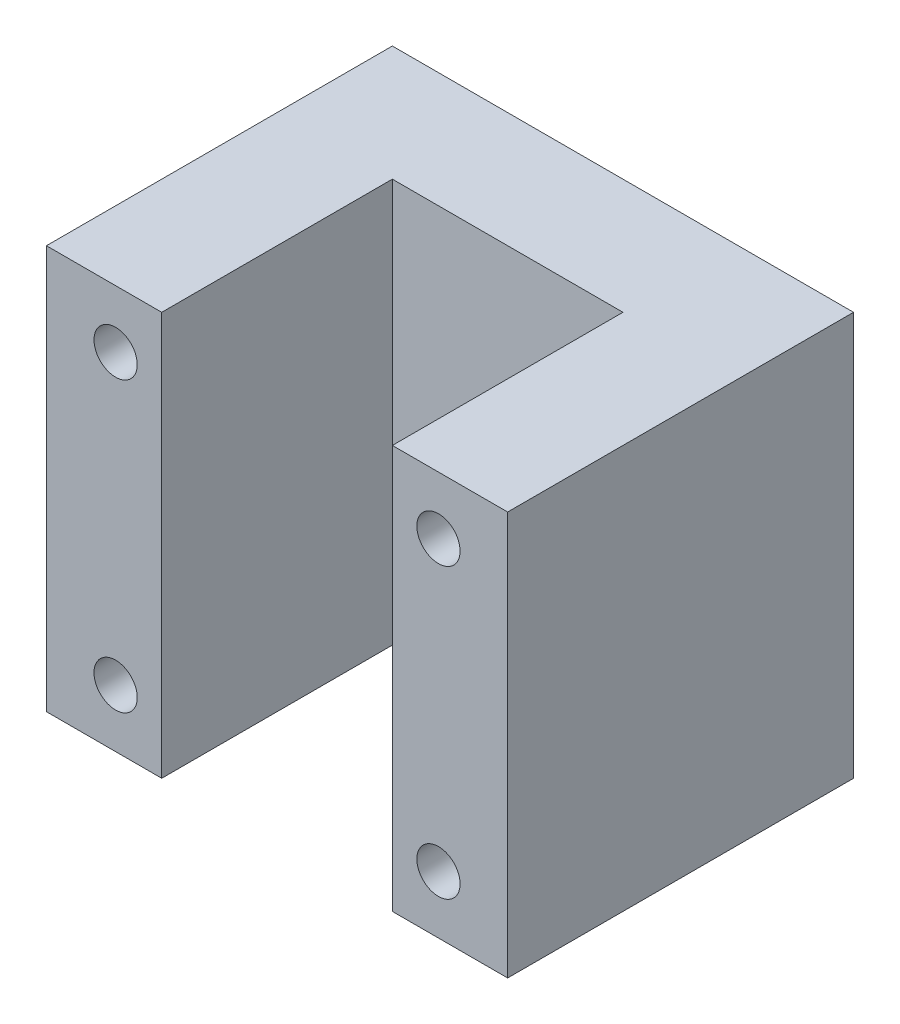
SolidWorks part; units mm, degrees
ref_plane "Front Plane" through (0, 0, 0) normal (0, 0, 1) x (1, 0, 0)
ref_plane "Top Plane" through (0, 0, 0) normal (0, 1, 0) x (1, 0, 0)
ref_plane "Right Plane" through (0, 0, 0) normal (1, 0, 0) x (0, 0, -1)
sketch "Sketch1" plane through (0, 0, 0) normal (0, 1, 0) x (1, 0, 0)
  line L0 (-20, 20) -> (20, 20)
  line L2 (-10, -10) -> (-10, 10)
  line L3 (-10, 10) -> (10, 10)
  line L4 (10, -10) -> (10, 10)
  line L5 (-10, -10) -> (10, 10) construction
  line L6 (-10, 10) -> (10, -10) construction
  line L7 (20, -10) -> (20, 20)
  line L9 (-20, -10) -> (-20, 20)
  line L13 (-20, -20) -> (20, -20) construction
  line L14 (-10, -10) -> (10, -10) construction
  line L15 (-10, -10) -> (-20, -10)
  line L16 (10, -10) -> (20, -10)
  line L17 (-20, -20) -> (-20, 20) construction
  line L18 (20, -20) -> (20, 20) construction
  point P0 (0, 0)
  point P10 (-20.5484, -12.6471)
  dimension "D1" = 20
  dimension "D2" = 20
  dimension "D3" = 10
extrude "Boss-Extrude1" add sketch "Sketch1" along normal mid plane 35
sketch "Sketch3" plane through (0, 0, 0) normal (0, 0, 1) x (1, 0, 0)
  circle A0 centre (-14, -12.5) radius 2.125 construction
  circle A1 centre (14, -12.5) radius 2.125 construction
  circle A2 centre (14, 12.5) radius 2.125 construction
  circle A3 centre (-14, 12.5) radius 2.125 construction
  circle A4 centre (-14, -12.5) radius 2.125
  circle A5 centre (14, -12.5) radius 2.125
  circle A6 centre (14, 12.5) radius 2.125
  circle A7 centre (-14, 12.5) radius 2.125
  circle A8 centre (-14, 12.5) radius 3.375
  circle A9 centre (14, 12.5) radius 3.375
  circle A10 centre (14, -12.5) radius 3.375
  circle A11 centre (-14, -12.5) radius 3.375
  circle A12 centre (0, 0) radius 3
  circle A13 centre (-14, 12.5) radius 1.875
  circle A14 centre (14, 12.5) radius 1.875
  circle A15 centre (-14, -12.5) radius 1.875
  circle A16 centre (14, -12.5) radius 1.875
  dimension "D2" = 6
  dimension "D1" = 1.25
  dimension "D3" = 1.5
extrude "Cut-Extrude1" cut sketch "Sketch3" along normal blind 10 and the other way through all from surface contours A8 A7 | A11 A4 | A10 A5 | A9 A6 | A6 | A5 | A4 | A7 region at (-16.0649, -12.5, 0) region at (11.9351, -12.5, 0) region at (11.9351, 12.5, 0) region at (-16.0649, 12.5, 0) region at (-17.2795, 12.5, 0) region at (10.7205, 12.5, 0) region at (10.7205, -12.5, 0) region at (-17.2795, -12.5, 0) starting at face at (0, 0, -20)
extrude "Cut-Extrude6" cut sketch "Sketch3<4>" against normal through all both and the other way through all contours A13 | A15 | A16 | A14 | A12 region at (0, 0, 0) region at (-14, 12.5, 0) region at (14, 12.5, 0) region at (-14, -12.5, 0) region at (14, -12.5, 0)
sketch "Sketch3<4>" plane through (0, 0, 0) normal (0, 0, 1) x (1, 0, 0) same geometry as "Sketch3"
